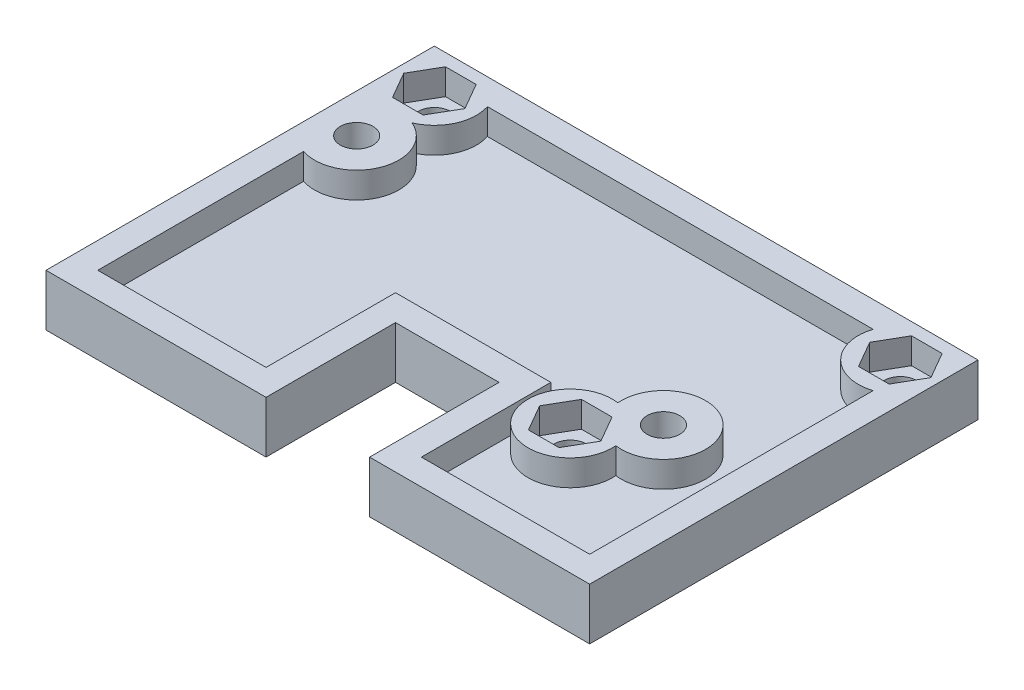
SolidWorks part; units mm, degrees
material "ABS PC"
ref_plane "Front Plane" through (0, 0, 0) normal (0, 0, 1) x (1, 0, 0)
ref_plane "Top Plane" through (0, 0, 0) normal (0, 1, 0) x (1, 0, 0)
ref_plane "Right Plane" through (0, 0, 0) normal (1, 0, 0) x (0, 0, -1)
sketch "Sketch1" plane through (0, 0, 0) normal (0, 1, 0) x (1, 0, 0)
  line L0 (-5.08, -6.35) -> (5.08, -6.35)
  line L1 (-26.67, -19.05) -> (-5.08, -19.05)
  line L2 (-26.67, -19.05) -> (-26.67, 19.05)
  line L3 (-5.08, -19.05) -> (-5.08, -6.35)
  line L4 (-26.67, 19.05) -> (26.67, 19.05)
  line L5 (5.08, -6.35) -> (5.08, -19.05)
  line L6 (-26.67, 19.05) -> (26.67, -19.05) construction
  line L7 (5.08, -19.05) -> (26.67, -19.05)
  line L16 (26.67, -19.05) -> (26.67, 19.05)
  circle A0 centre (12.065, -6.35) radius 1.6
  circle A1 centre (-22.86, 15.24) radius 1.6
  circle A2 centre (16.764, -1.905) radius 1.6
  circle A8 centre (-22.86, 7.62) radius 1.6
  circle A9 centre (22.86, 15.24) radius 1.6
  point P12 (-26.67, -19.05)
  point P33 (-19.05, -19.05)
  point P37 (19.05, -19.05)
  point P40 (26.67, -19.05)
  point P43 (26.67, 20.32)
  point P46 (19.05, 20.32)
  point P49 (-19.05, 20.32)
  point P52 (-26.67, 20.32)
  dimension "D3" = 17.145
  dimension "D4" = 3.2
  dimension "D7" = 38.1
  dimension "D10" = 14.605
  dimension "D18" = 3.81
  dimension "D1" = 10.16
  dimension "D5" = 9.906
  dimension "D8" = 3.81
  dimension "D15" = 3.2
  dimension "D2" = 12.7
  dimension "D6" = 3.81
  dimension "D9" = 3.81
  dimension "D11" = 11.43
  dimension "D12" = 3.81
  dimension "D13" = 12.7
  dimension "D14" = 53.34
  dimension "D16" = 21.59
extrude "Boss-Extrude1" add sketch "Sketch1" along normal blind 5.08
shell "Shell1" thickness 2.54 removed face at (-22.86, 5.08, -6.02)
sketch "Sketch8" plane through (0, 5.08, 0) normal (0, 1, 0) x (1, 0, 0)
  line L1 (-19.8578, 15.24) -> (-21.3589, 17.84)
  line L2 (-21.3589, 17.84) -> (-24.3611, 17.84)
  line L3 (-24.3611, 17.84) -> (-25.8622, 15.24)
  line L4 (-25.8622, 15.24) -> (-24.3611, 12.64)
  line L5 (-24.3611, 12.64) -> (-21.3589, 12.64)
  line L6 (-21.3589, 12.64) -> (-19.8578, 15.24)
  line L7 (25.8622, 15.24) -> (24.3611, 17.84)
  line L8 (24.3611, 17.84) -> (21.3589, 17.84)
  line L9 (21.3589, 17.84) -> (19.8578, 15.24)
  line L10 (19.8578, 15.24) -> (21.3589, 12.64)
  line L11 (21.3589, 12.64) -> (24.3611, 12.64)
  line L12 (24.3611, 12.64) -> (25.8622, 15.24)
  line L13 (15.0672, -6.35) -> (13.5661, -3.75)
  line L14 (13.5661, -3.75) -> (10.5639, -3.75)
  line L15 (10.5639, -3.75) -> (9.0628, -6.35)
  line L16 (9.0628, -6.35) -> (10.5639, -8.95)
  line L17 (10.5639, -8.95) -> (13.5661, -8.95)
  line L18 (13.5661, -8.95) -> (15.0672, -6.35)
  circle A0 centre (-22.86, 15.24) radius 2.6 construction
  circle A1 centre (22.86, 15.24) radius 2.6 construction
  circle A2 centre (12.065, -6.35) radius 2.6 construction
  dimension "D1" = 5.2
  dimension "D2" = 5.2
  dimension "D3" = 5.2
extrude "Cut-Extrude1" cut sketch "Sketch8" against normal blind 2.54
